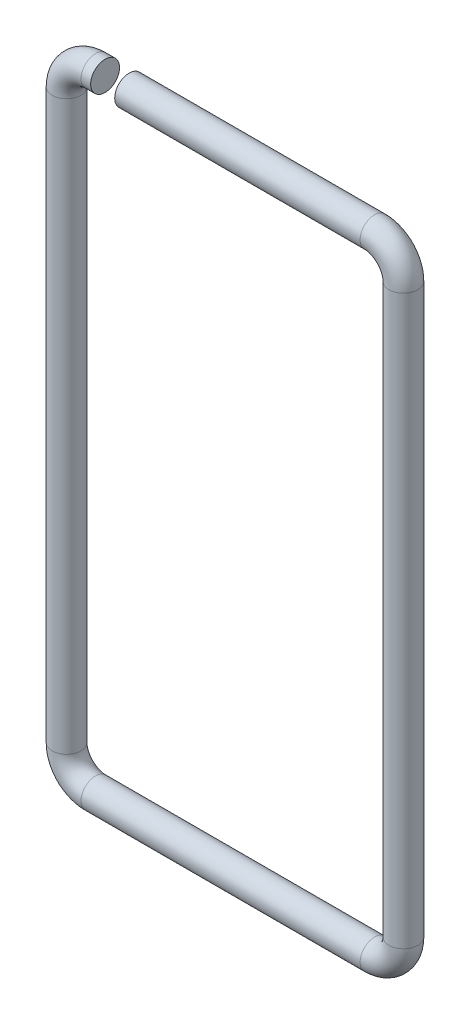
SolidWorks part; units mm, degrees
material "AISI 1020"
ref_plane "Plano frontal" through (0, 0, 0) normal (0, 0, 1) x (1, 0, 0)
ref_plane "Plano superior" through (0, 0, 0) normal (0, 1, 0) x (1, 0, 0)
ref_plane "Plano direito" through (0, 0, 0) normal (1, 0, 0) x (0, 0, -1)
sketch "Esboço1" plane through (0, 0, 0) normal (0, 0, 1) x (1, 0, 0)
  line L0 (-35, 35.0231) -> (-35, -82.9769)
  line L1 (-22, 41.0231) -> (29, 41.0231)
  line L2 (0, 0) -> (0, -88.9769) construction
  line L3 (-29, -88.9769) -> (29, -88.9769)
  line L4 (35, 35.0231) -> (35, -82.9769)
  line L5 (-27, 41.0231) -> (-29, 41.0231)
  arc A0 (35, 35.0231) -> (29, 41.0231) centre (29, 35.0231) ccw
  arc A1 (-35, 35.0231) -> (-29, 41.0231) centre (-29, 35.0231) cw
  arc A2 (-29, -88.9769) -> (-35, -82.9769) centre (-29, -82.9769) cw
  arc A3 (35, -82.9769) -> (29, -88.9769) centre (29, -82.9769) cw
  point P11 (35, 41.0231)
  point P14 (-35, 41.0231)
  point P17 (-35, -88.9769)
  point P20 (35, -88.9769)
  dimension "D2" = 6
  dimension "D1" = 8
  dimension "D3" = 130
  dimension "D4" = 70
  dimension "D5" = 5
ref_plane "Plano1" through (-22, 41.0231, 0) normal (1, 0, 0) x (0, 0, -1)
sketch "Esboço2" plane through (-22, 41.0231, 0) normal (1, 0, 0) x (0, 0, -1)
  circle A0 centre (0, 0) radius 3
  dimension "D1" = 6
sweep "Varredura1" add profiles "Esboço2" path "Esboço1"
ref_axis "Eixo1" through (29, 41.0231, 0) along (-1, 0, 0)
